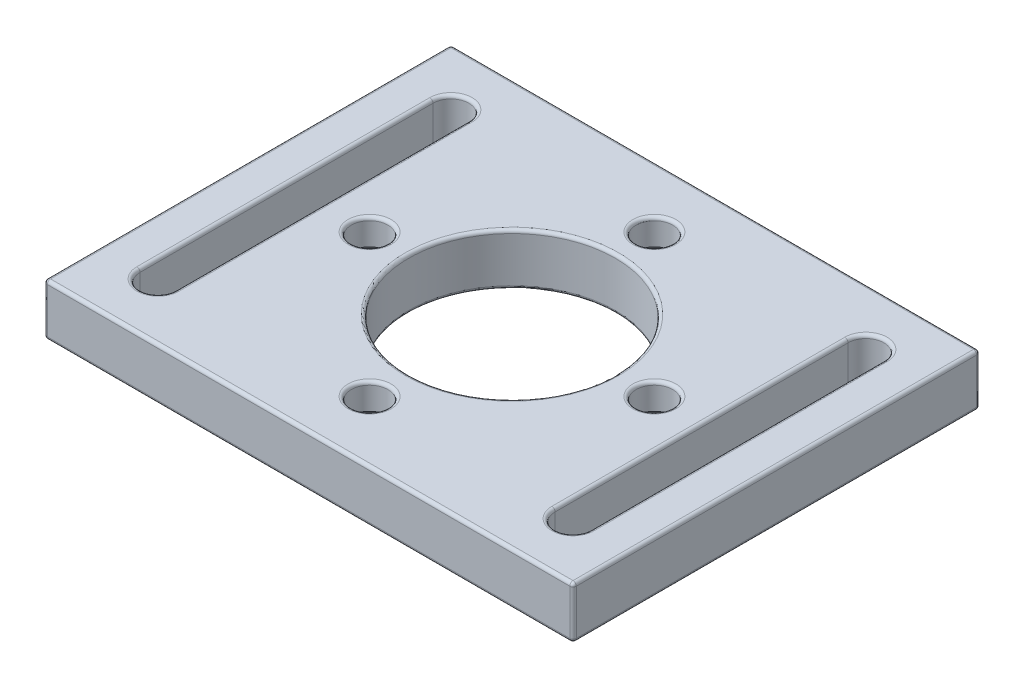
SolidWorks part; units mm, degrees
ref_plane "Front Plane" through (0, 0, 0) normal (0, 0, 1) x (1, 0, 0)
ref_plane "Top Plane" through (0, 0, 0) normal (0, 1, 0) x (1, 0, 0)
ref_plane "Right Plane" through (0, 0, 0) normal (1, 0, 0) x (0, 0, -1)
sketch "Sketch2" plane through (0, 0, 0) normal (0, 1, 0) x (1, 0, 0)
  line L0 (-25.5, 18) -> (-25.5, -18) construction
  line L1 (32.5, -25) -> (-32.5, -25)
  line L2 (32.5, -25) -> (32.5, 25)
  line L3 (32.5, 25) -> (-32.5, 25)
  line L4 (-32.5, -25) -> (-32.5, 25)
  line L5 (32.5, -25) -> (-32.5, 25) construction
  line L6 (32.5, 25) -> (-32.5, -25) construction
  line L7 (-23.3, 18) -> (-23.3, -18)
  line L8 (-27.7, 18) -> (-27.7, -18)
  line L9 (-25.5, 0) -> (0, 0) construction
  line L10 (0, 0) -> (0, -25) construction
  line L11 (25.5, 18) -> (25.5, -18) construction
  line L12 (23.3, 18) -> (23.3, -18)
  line L13 (27.7, 18) -> (27.7, -18)
  arc A0 (-23.3, 18) -> (-27.7, 18) centre (-25.5, 18) ccw
  arc A1 (-27.7, -18) -> (-23.3, -18) centre (-25.5, -18) ccw
  circle A2 centre (0, 0) radius 12.7
  arc A3 (23.3, 18) -> (27.7, 18) centre (25.5, 18) cw
  arc A4 (27.7, -18) -> (23.3, -18) centre (25.5, -18) cw
  point P0 (0, 0)
  point P8 (-25.5, 0)
  point P19 (25.5, 0)
  dimension "D3" = 2.2
  dimension "D6" = 25.4
  dimension "D1" = 65
  dimension "D2" = 50
  dimension "D4" = 36
  dimension "D5" = 25.5
extrude "Boss-Extrude1" add sketch "Sketch2" along normal blind 6.35
sketch "Sketch3" plane through (0, 0, 0) normal (1, 0, 0) x (0, 0, -1)
  line L0 (12.8, 0) -> (17.5, 0)
  line L1 (25, 0) -> (-25, 0) construction
  line L2 (12.8, 0) -> (15.25, 3.175)
  line L3 (15.25, 3.175) -> (15.25, 6.35)
  line L4 (25, 6.35) -> (-25, 6.35) construction
  line L5 (15.25, 6.35) -> (17.5, 6.35)
  line L6 (17.5, 0) -> (17.5, 6.35) construction
  line L7 (17.5, 0) -> (17.5, 6.35)
  dimension "D1" = 2.25
  dimension "D2" = 4.7
  dimension "D3" = 3.175
  dimension "D4" = 17.5
revolve "Cut-Revolve1" cut sketch "Sketch3" angle 360 about L6
pattern_circular "CirPattern1" count 4 over 360 about axis through (0, 6.35, 0) along (0, 1, 0) of "Cut-Revolve1"
fillet "Fillet1" radius 0.4 34 edges at (-25.5, 6.35, 20.2) (-27.7, 6.35, 0) (-25.5, 6.35, -20.2) (-25.5, 0, 20.2) (-27.7, 0, 0) (-25.5, 0, -20.2) (25.5, 6.35, 20.2) (23.3, 6.35, 0) (25.5, 6.35, -20.2) (25.5, 0, 20.2) (23.3, 0, 0) (25.5, 0, -20.2) (0, 0, 12.7) (0, 6.35, 12.7) (-32.5, 6.35, 0) (-32.5, 0, 0) (0, 6.35, -25) (-32.5, 3.175, -25) (0, 0, -25) (32.5, 6.35, 0) (32.5, 3.175, -25) (32.5, 0, 0) (-32.5, 3.175, 25) (0, 6.35, 25) (32.5, 3.175, 25) (0, 0, 25) (-23.3, 6.35, 0) (-23.3, 0, 0) (27.7, 6.35, 0) (27.7, 0, 0) (0, 6.35, -19.75) (19.75, 6.35, 0) (-19.75, 6.35, 0) (0, 6.35, 19.75)
